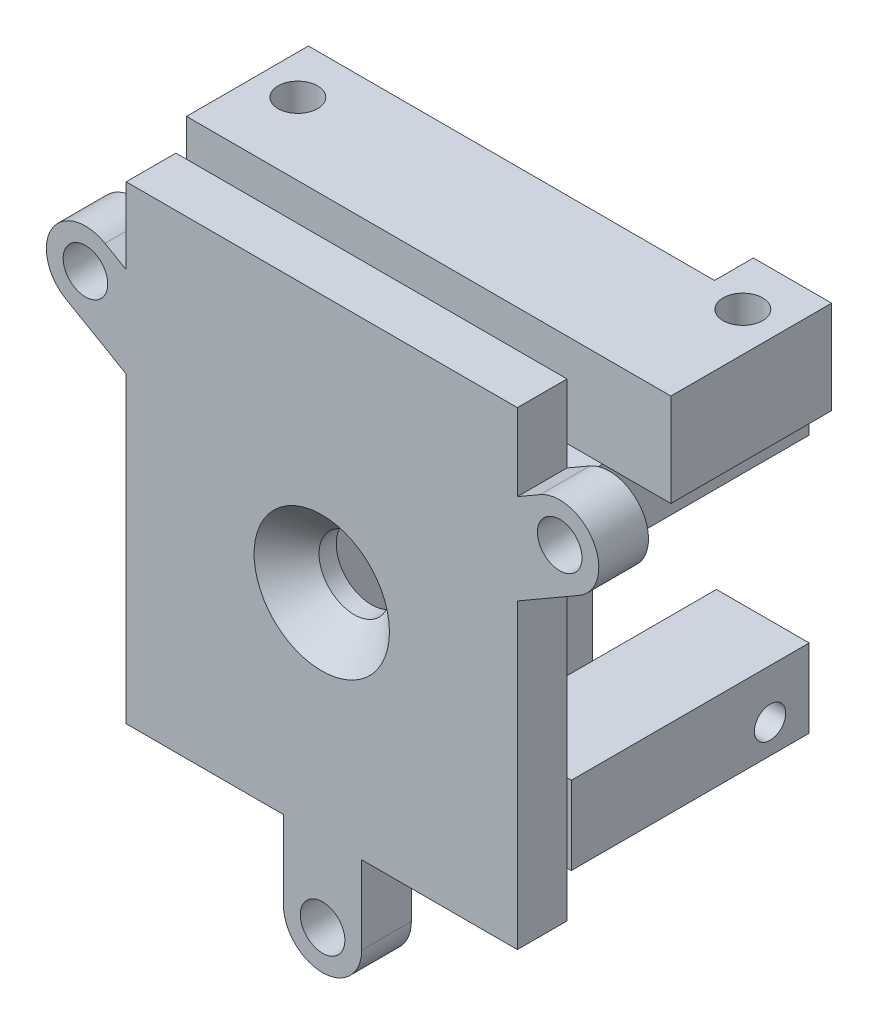
SolidWorks part; units mm, degrees
ref_plane "Front Plane" through (0, 0, 0) normal (0, 0, 1) x (1, 0, 0)
ref_plane "Top Plane" through (0, 0, 0) normal (0, 1, 0) x (1, 0, 0)
ref_plane "Right Plane" through (0, 0, 0) normal (1, 0, 0) x (0, 0, -1)
sketch "Sketch1" plane through (0, 0, 0) normal (0, 0, 1) x (1, 0, 0)
  line L5 (-5, 30) -> (5, 30)
  line L6 (-25, 30) -> (-5, 30)
  line L13 (-25, -30) -> (-4.8977, -30)
  line L31 (5.1023, -30) -> (25, -30)
  line L37 (-4.8977, -30) -> (-4.8977, -40)
  line L39 (5.1023, -30) -> (5.1023, -40)
  line L40 (0.1023, 0) -> (0.1023, -12.7655) construction
  line L41 (0.1023, 0) -> (-30.2086, 17.5) construction
  line L42 (0.1023, 0) -> (30.4132, 17.5) construction
  line L45 (5, 30) -> (25, 30)
  line L61 (25, 30) -> (25, 20.1482)
  line L62 (-25, 30) -> (-25, 20.2663)
  line L63 (-25, 8.7193) -> (-25, -30)
  line L65 (-27.7086, 21.8301) -> (-25, 20.2663)
  line L66 (-32.7086, 13.1699) -> (-25, 8.7193)
  line L67 (27.9132, 21.8301) -> (25, 20.1482)
  line L68 (32.9132, 13.1699) -> (25, 8.6012)
  line L69 (25, 8.6012) -> (25, -30)
  arc A20 (-4.8977, -40) -> (5.1023, -40) centre (0.1023, -40) ccw
  circle A21 centre (0.1023, -40) radius 2.85
  circle A22 centre (30.4132, 17.5) radius 2.85
  circle A23 centre (-30.2086, 17.5) radius 2.85
  arc A29 (-27.7086, 21.8301) -> (-32.7086, 13.1699) centre (-30.2086, 17.5) ccw
  arc A30 (32.9132, 13.1699) -> (27.9132, 21.8301) centre (30.4132, 17.5) ccw
  dimension "D1" = 50
  dimension "D2" = 60
  dimension "D3" = 25
  dimension "D7" = 30
  dimension "D5" = 10
  dimension "D6" = 10
  dimension "D9" = 5
  dimension "D10" = 5.7
  dimension "D11" = 120
  dimension "D12" = 120
  dimension "D13" = 25.1023
  dimension "D15" = 30.3109
  dimension "D14" = 10
  dimension "D17" = 10
  dimension "D16" = 8.9012
  dimension "D4" = 10
  dimension "D8" = 5
  dimension "D18" = 26.4769
  dimension "D19" = 32.1827
  dimension "D20" = 2.7086
  dimension "D21" = 26.4382
  dimension "D22" = 7.9132
  dimension "D23" = 32.1084
  dimension "D24" = 2.9132
extrude "Boss-Extrude1" add sketch "Sketch1" along normal blind 6.35
sketch "Sketch2" plane through (0, 0, 0) normal (0, 0, -1) x (-1, 0, 0)
  line L0 (-12.7, 34.75) -> (12.7, 34.75)
  line L2 (-12.7, 34.75) -> (-12.7, -34.75)
  line L3 (-12.7, -34.75) -> (12.7, -34.75)
  line L4 (12.7, 34.75) -> (12.7, -34.75)
  line L5 (-7.35, 23.4) -> (7.35, 23.4)
  line L6 (-7.35, 23.4) -> (-7.35, -29.4)
  line L7 (-7.35, -29.4) -> (7.35, -29.4)
  line L8 (7.35, 23.4) -> (7.35, -29.4)
  point P8 (-12.7, 0)
  point P13 (0, -34.75)
  dimension "D3" = 14.7
  dimension "D1" = 69.5
  dimension "D2" = 25.4
  dimension "D4" = 5.35
  dimension "D5" = 5.35
  dimension "D6" = 52.8
extrude "Boss-Extrude2" add sketch "Sketch2" along normal blind 15.5784
hole_wizard "CSK for M8 Flat Head Machine Screw1" positions "Sketch3" profile "Sketch4" countersink size "M8" standard "ANSI Metric"
sketch "Sketch3" plane through (0, 0, 6.35) normal (0, 0, 1) x (1, 0, 0)
  point P5 (0, -3)
  dimension "D1" = 3
sketch "Sketch4" plane through (0, -3, 6.35) normal (1, 0, 0) x (0, -1, 0)
  line L0 (0, 0) -> (0, 20.2039)
  line L1 (0, 20.2039) -> (4.5, 17.5)
  line L2 (4.5, 17.5) -> (4.5, 4.15)
  line L3 (4.5, 4.15) -> (8.65, 0)
  line L5 (8.65, 0) -> (0, 0)
  line L6 (-4.5, 4.15) -> (-8.65, 0) construction
  line L10 (0, 20.2039) -> (-4.5, 17.5) construction
  line L11 (0, -6.35) -> (0, 107.95) construction
  dimension "Hole Dia." = 9
  dimension "Hole Depth" = 17.5
  dimension "Near C'Sink Dia." = 17.3
  dimension "Near C'Sink Angle" = 90
  dimension "Drill Angle" = 118
sketch "Sketch6" plane through (12.7, 0, 0) normal (1, 0, 0) x (0, 0, -1)
  line L0 (15.5784, 34.75) -> (15.5784, -34.75) construction
  line L1 (0, 34.75) -> (15.5784, 34.75)
  line L2 (0, 34.75) -> (0, 22.85)
  line L3 (0, 22.85) -> (15.5784, 22.85)
  line L4 (15.5784, 34.75) -> (15.5784, 22.85)
  dimension "D1" = 11.9
extrude "Boss-Extrude3" add sketch "Sketch6" along normal blind 25.5721
sketch "Sketch7" plane through (-12.7, 0, 0) normal (-1, 0, 0) x (0, 0, 1)
  line L1 (-15.5784, 34.75) -> (0, 34.75)
  line L2 (-15.5784, 34.75) -> (-15.5784, 22.85)
  line L3 (-15.5784, 22.85) -> (0, 22.85)
  line L4 (0, 34.75) -> (0, 22.85)
  dimension "D1" = 11.9
extrude "Boss-Extrude4" add sketch "Sketch7" along normal blind 10.9373
sketch "Sketch8" plane through (0, 34.75, 0) normal (0, 1, 0) x (1, 0, 0)
  line L1 (-23.6373, 0) -> (-23.6373, 15.5784) construction
  line L3 (-23.6373, 15.5784) -> (38.2721, 15.5784) construction
  circle A0 centre (-18.6373, 9.2284) radius 2.5273
  dimension "D1" = 5.0546
  dimension "D2" = 6.35
  dimension "D3" = 5
extrude "Cut-Extrude1" cut sketch "Sketch8" against normal blind 7
sketch "Sketch9" plane through (0, 0, -15.5784) normal (0, 0, -1) x (-1, 0, 0)
  line L1 (-38.2721, 34.75) -> (-28.2721, 34.75)
  line L2 (-38.2721, 34.75) -> (-38.2721, 22.85)
  line L3 (-38.2721, 22.85) -> (-28.2721, 22.85)
  line L4 (-28.2721, 34.75) -> (-28.2721, 22.85)
  dimension "D1" = 10
extrude "Boss-Extrude5" add sketch "Sketch9" along normal blind 4.9727
sketch "Sketch10" plane through (0, 34.75, 0) normal (0, 1, 0) x (1, 0, 0)
  line L0 (38.2721, 20.5511) -> (38.2721, 0) construction
  line L1 (28.2721, 20.5511) -> (38.2721, 20.5511) construction
  circle A0 centre (33.2721, 14.2011) radius 2.5273
  circle A1 centre (-18.6373, 9.2284) radius 2.5273 construction
  dimension "D1" = 5
  dimension "D2" = 6.35
extrude "Cut-Extrude2" cut sketch "Sketch10" against normal blind 7
sketch "Sketch11" plane through (12.7, 0, 0) normal (1, 0, 0) x (0, 0, -1)
  line L0 (15.5784, 22.85) -> (15.5784, -34.75) construction
  line L1 (15.5784, -3.175) -> (20.9169, -3.175)
  line L2 (15.5784, -3.175) -> (15.5784, -13.175)
  line L3 (15.5784, -13.175) -> (20.9169, -13.175)
  line L4 (20.9169, -3.175) -> (20.9169, -13.175)
  line L5 (0, 22.85) -> (20.5511, 22.85) construction
  dimension "D1" = 26.025
  dimension "D2" = 10
  dimension "D3" = 5.3384
extrude "Boss-Extrude6" add sketch "Sketch11" against normal up to surface (5.35 mm away) up to face at (7.35, -3, -7.7892)
sketch "Sketch12" plane through (12.7, 0, 0) normal (1, 0, 0) x (0, 0, -1)
  line L5 (0, 22.85) -> (20.5511, 22.85) construction
  line L6 (8.7892, 17.85) -> (1, 17.85)
  line L7 (8.7892, 17.85) -> (8.7892, 7.85)
  line L8 (8.7892, 7.85) -> (1, 7.85)
  line L9 (1, 17.85) -> (1, 7.85)
  line L11 (8.7892, -15.15) -> (1, -15.15)
  line L12 (8.7892, -15.15) -> (8.7892, -25.15)
  line L13 (8.7892, -25.15) -> (1, -25.15)
  line L14 (1, -15.15) -> (1, -25.15)
  line L16 (0, 22.85) -> (0, -30) construction
  dimension "D3" = 7.7892
  dimension "D4" = 10
  dimension "D5" = 43
  dimension "D6" = 10
  dimension "D7" = 1
  dimension "D10" = 5
extrude "Boss-Extrude7" add sketch "Sketch12" along normal blind 11.85
sketch "Sketch14" plane through (0, 0, -20.9169) normal (0, 0, -1) x (-1, 0, 0)
  line L6 (-12.7, -3.175) -> (-7.35, -3.175)
  line L7 (-12.7, -3.175) -> (-12.7, -13.175)
  line L8 (-12.7, -13.175) -> (-7.35, -13.175)
  line L9 (-7.35, -3.175) -> (-7.35, -13.175)
extrude "Cut-Extrude4" cut sketch "Sketch14" against normal up to surface (5.3384 mm away) up to face at (3.0856, 2.9188, -15.5784)
sketch "Sketch15" plane through (0, 0, -8.7892) normal (0, 0, -1) x (-1, 0, 0)
  line L5 (-12.7, 7.85) -> (-12.7, 17.85) construction
  line L6 (-24.55, -15.15) -> (-12.7, -15.15)
  line L7 (-24.55, -15.15) -> (-24.55, -25.15)
  line L8 (-24.55, -25.15) -> (-12.7, -25.15)
  line L9 (-12.7, -15.15) -> (-12.7, -25.15)
  line L10 (-24.55, 17.85) -> (-12.7, 17.85)
  line L11 (-24.55, 17.85) -> (-24.55, 7.85)
  line L12 (-24.55, 7.85) -> (-12.7, 7.85)
  line L13 (-12.7, 17.85) -> (-12.7, 7.85)
  line L14 (-24.55, 7.85) -> (-12.7, 7.85) construction
extrude "Boss-Extrude8" add sketch "Sketch15" along normal blind 22.6108
sketch "Sketch16" plane through (24.55, 0, 0) normal (1, 0, 0) x (0, 0, -1)
  line L0 (1, -25.15) -> (31.4, -25.15) construction
  line L1 (31.4, -15.15) -> (31.4, -25.15) construction
  line L4 (31.4, 17.85) -> (1, 17.85) construction
  line L5 (31.4, 17.85) -> (31.4, 7.85) construction
  circle A0 centre (26.4, -21.43) radius 2
  circle A1 centre (26.4, 14.13) radius 2
  point P8 (0, 0)
  dimension "D1" = 3.72
  dimension "D3" = 4
  dimension "D4" = 3.72
  dimension "D2" = 5
  dimension "D5" = 5
extrude "Cut-Extrude7" cut sketch "Sketch16" against normal blind 6
